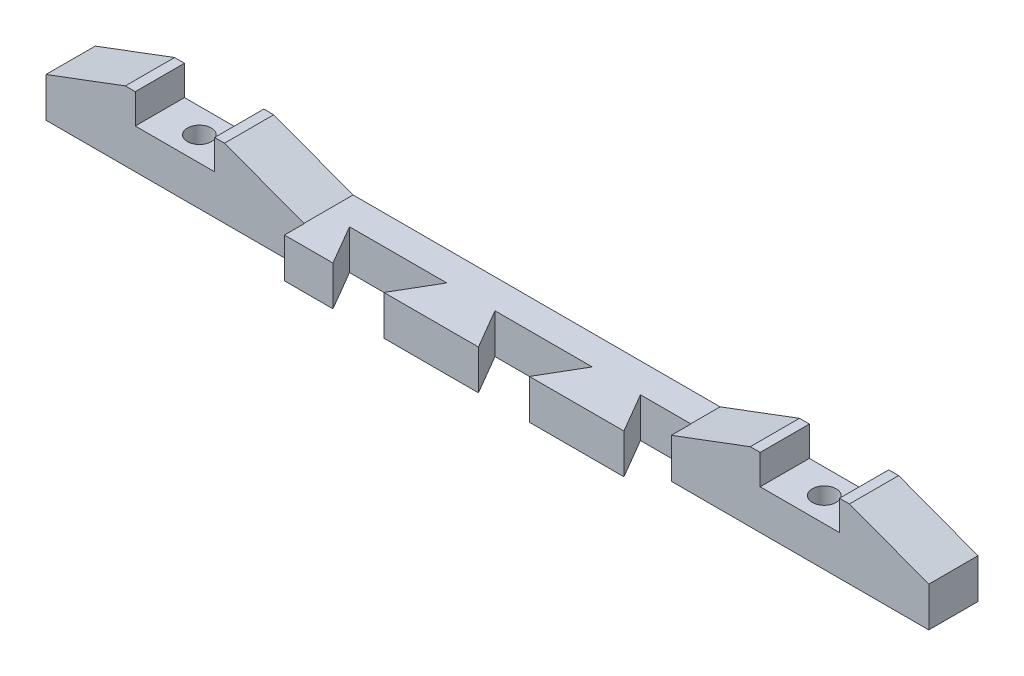
SolidWorks part; units mm, degrees
other "标注1"
sketch "草图3" plane through (-22.25, 4, -10) normal (-0.231, 0.6469, -0.7268) x (-0.9696, -0.2151, 0.1167)
ref_plane "前视基准面" through (0, 0, 0) normal (0, 0, 1) x (1, 0, 0)
ref_plane "上视基准面" through (0, 0, 0) normal (0, 1, 0) x (1, 0, 0)
ref_plane "右视基准面" through (0, 0, 0) normal (1, 0, 0) x (0, 0, -1)
other "Configuration Table"
sketch "草图4" plane through (0, 0, 0) normal (0, 0, 1) x (1, 0, 0)
  line L6 (8.5, -1.5) -> (17.75, -1.5)
  line L11 (17.75, -1.5) -> (17.75, -3.5)
  line L16 (17.75, -3.5) -> (-4.5, -3.5)
  line L17 (-4.5, -3.5) -> (-4.5, -1.5)
  line L19 (0, 0) -> (0, -1.5)
  line L20 (0, -1.5) -> (4, -1.5)
  line L21 (4, -1.5) -> (4, 0)
  line L26 (4, 0) -> (4.5, 0)
  line L27 (4.5, 0) -> (8.5, -1.5)
  line L28 (0, 0) -> (-0.5, 0)
  line L29 (-0.5, 0) -> (-4.5, -1.5)
  dimension "D2" = 4
  dimension "D4" = 0.5
  dimension "D5" = 2
  dimension "D6" = 2
  dimension "D7" = 4
  dimension "D8" = 1.5
  dimension "D9" = 4
  dimension "D10" = 22.25
extrude "凸台-拉伸1" add sketch "草图4" along normal blind 2.5 contours L28 L29 L17 L16 L11 L6 L27 L26 L21 L20 L19 | L19 | L21 region at (5.9579, -2.2764, 0)
sketch "草图5" plane through (0, -1.5, 0) normal (0, 1, 0) x (1, 0, 0)
  line L0 (0, 0) -> (4, -2.5) construction
  line L1 (0, -2.5) -> (0, 0) construction
  line L2 (0, -2.5) -> (4, -2.5) construction
  line L3 (4, -2.5) -> (4, 0) construction
  line L4 (0, 0) -> (4, 0) construction
  circle A0 centre (2, -1.25) radius 0.6
  circle A1 centre (2, -1.25) radius 1
  dimension "D1" = 1.2
  dimension "D2" = 2
extrude "切除-拉伸1" cut sketch "草图5" against normal through all contours A0
extrude "切除-拉伸2" cut sketch "草图5<3>" along normal blind 1 from surface contours A1 starting at face at (2, -3.5, 1.85)
sketch "草图5<3>" plane through (0, -1.5, 0) normal (0, 1, 0) x (1, 0, 0) same geometry as "草图5"
mirror "镜向1" about plane through (0, 0, 2.5) normal (0, 0, 1) of bodies 215 203
mirror "镜向2" about plane through (17.75, 0, 2.5) normal (1, 0, 0) of bodies 204
sketch "草图6" plane through (0, -1.5, 0) normal (0, 1, 0) x (1, 0, 0)
  line L1 (9.8333, -1.5) -> (11, -3.5)
  line L2 (11, -3.5) -> (13.5, -3.5) construction
  line L3 (18.3333, -3.5) -> (20.8333, -3.5) construction
  line L4 (9.8333, -1.5) -> (14.6667, -1.5)
  line L5 (14.6667, -1.5) -> (13.5, -3.5)
  line L6 (13.5, -3.5) -> (18.3333, -3.5)
  line L7 (18.3333, -3.5) -> (17.1667, -1.5)
  line L8 (17.1667, -1.5) -> (22, -1.5)
  line L9 (11, -3.5) -> (8.5, -3.5)
  line L10 (8.5, -5) -> (8.5, 0) construction
  line L11 (22, -1.5) -> (20.8333, -3.5)
  line L12 (20.8333, -3.5) -> (25.6667, -3.5)
  line L13 (25.6667, -3.5) -> (24.5, -1.5)
  line L14 (24.5, -1.5) -> (27, -1.5)
  line L15 (-4.5, -2.5) -> (8.5, -2.5)
  line L16 (14.6667, -1.5) -> (17.1667, -1.5) construction
  line L17 (22, -1.5) -> (24.5, -1.5) construction
  line L18 (12.25, -3.5) -> (12.25, -1.5) construction
  line L19 (27, -5) -> (27, 0) construction
  line L20 (8.5, -2.5) -> (12.25, -2.5) construction
  line L21 (-4.5, -5) -> (-4.5, 0) construction
  line L22 (8.5, -2.5) -> (8.5, -3.5)
  line L23 (27, -1.5) -> (27, -2.5)
  line L24 (27, -2.5) -> (40, -2.5)
  line L25 (40, -5) -> (40, 0) construction
  line L26 (-4.5, -2.5) -> (-4.5, 0)
  line L27 (-4.5, 0) -> (40, 0)
  line L28 (40, 0) -> (40, -2.5)
  line L29 (-4.5, -2.5) -> (-4.5, -5)
  line L30 (-4.5, -5) -> (40, -5)
  line L31 (40, -5) -> (40, -2.5)
  line M2 (8.5, 0) -> (8.5, -5)
  line M3 (8.5, -5) -> (27, -5)
  line M4 (27, -5) -> (27, 0)
  dimension "D1" = 2
  dimension "D2" = 2.5
extrude "切除-拉伸6" cut sketch "草图6" against normal through all both and the other way through all contours L29 L30 L15 M2 | L14 L13 L12 L11 L8 L7 L6 L5 L4 L1 L9 M2 M3 M4 | L30 L31 L24 M4 region at (17.8534, -1.5, 3.508) region at (2, -1.5, 3.75) region at (33.5, -1.5, 3.75)
sketch "草图7" plane through (0, -1.5, 0) normal (0, 1, 0) x (1, 0, 0)
  line L0 (-4.5, -2.48) -> (8.52, -2.48)
  line L1 (-4.5, -2.5) -> (-4.5, 0) construction
  line L2 (8.52, -2.48) -> (8.52, -3.48)
  line L3 (8.52, -3.48) -> (10.9652, -3.48)
  line L4 (10.9652, -3.48) -> (9.7985, -1.48)
  line L5 (9.7985, -1.48) -> (14.7015, -1.48)
  line L6 (14.7015, -1.48) -> (13.5348, -3.48)
  line L7 (13.5348, -3.48) -> (18.2985, -3.48)
  line L8 (18.2985, -3.48) -> (17.1318, -1.48)
  line L9 (17.1318, -1.48) -> (22.0348, -1.48)
  line L10 (22.0348, -1.48) -> (20.8682, -3.48)
  line L11 (20.8682, -3.48) -> (25.6318, -3.48)
  line L12 (25.6318, -3.48) -> (24.4652, -1.48)
  line L13 (24.4652, -1.48) -> (27.02, -1.48)
  line L14 (27.02, -1.48) -> (27.02, -2.48)
  line L15 (27.02, -2.48) -> (40, -2.48)
  line L16 (40, -2.5) -> (40, 0) construction
  line L17 (40, -2.5) -> (36, -2.5) construction
  line L18 (27, -2.5) -> (27, -1.5) construction
  line L19 (24.5, -1.5) -> (27, -1.5) construction
  line L21 (14.6667, -1.5) -> (13.5, -3.5) construction
  line L22 (20.8333, -3.5) -> (25.6667, -3.5) construction
  line L23 (8.5, -3.5) -> (8.5, -2.5) construction
  line L25 (9.8333, -1.5) -> (11, -3.5) construction
  line L26 (18.3333, -3.5) -> (17.1667, -1.5) construction
  line L27 (22, -1.5) -> (20.8333, -3.5) construction
  line L28 (25.6667, -3.5) -> (24.5, -1.5) construction
  line L29 (-4.5, -2.48) -> (-4.5, -2.5)
  line L30 (-4.5, -2.5) -> (8.5, -2.5)
  line L31 (8.5, -2.5) -> (8.5, -3.5)
  line L32 (8.5, -3.5) -> (11, -3.5)
  line L33 (11, -3.5) -> (9.8333, -1.5)
  line L34 (9.8333, -1.5) -> (14.6667, -1.5)
  line L35 (14.6667, -1.5) -> (13.5, -3.5)
  line L36 (13.5, -3.5) -> (18.3333, -3.5)
  line L37 (18.3333, -3.5) -> (17.1667, -1.5)
  line L38 (17.1667, -1.5) -> (22, -1.5)
  line L39 (22, -1.5) -> (20.8333, -3.5)
  line L40 (20.8333, -3.5) -> (25.6667, -3.5)
  line L41 (25.6667, -3.5) -> (24.5, -1.5)
  line L42 (24.5, -1.5) -> (27, -1.5)
  line L43 (27, -1.5) -> (27, -2.5)
  line L44 (27, -2.5) -> (40, -2.5)
  line L45 (40, -2.5) -> (40, -2.48)
  dimension "D1" = 0.02
  dimension "D2" = 0.02
  dimension "D3" = 0.02
  dimension "D4" = 0.02
  dimension "D5" = 0.02
  dimension "D6" = 0.02
  dimension "D7" = 0.02
  dimension "D8" = 0.02
  dimension "D9" = 0.02
  dimension "D10" = 0.02
extrude "切除-拉伸7" cut sketch "草图7" against normal through all both and the other way through all
